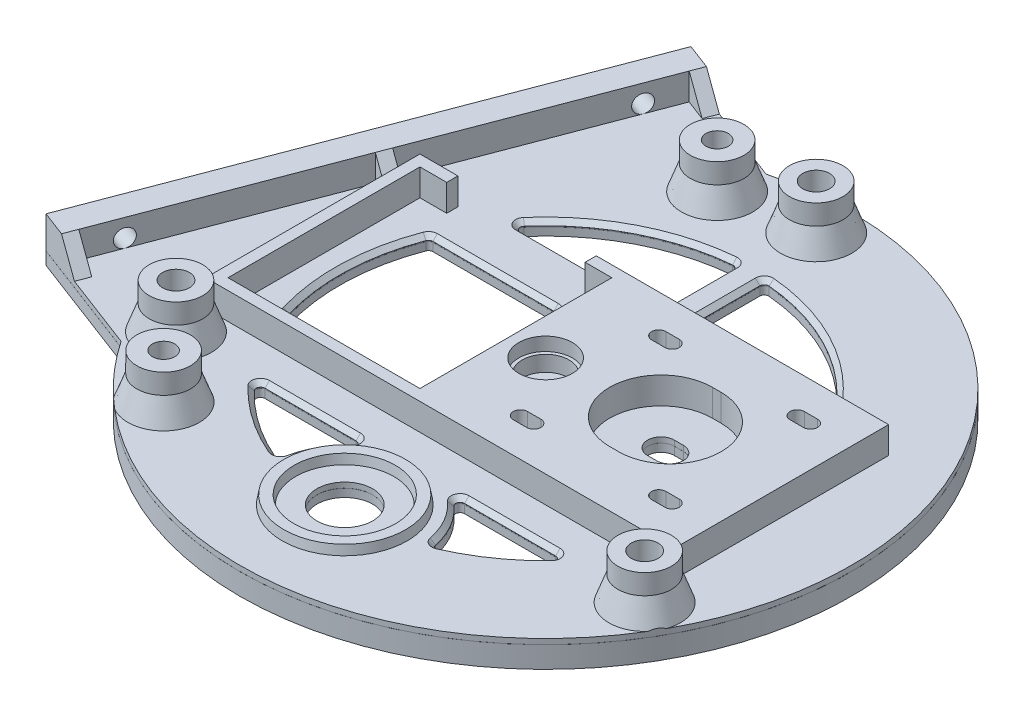
SolidWorks part; units mm, degrees
material "ABS"
ref_plane "Front Plane" through (0, 0, 0) normal (0, 0, 1) x (1, 0, 0)
ref_plane "Top Plane" through (0, 0, 0) normal (0, 1, 0) x (1, 0, 0)
ref_plane "Right Plane" through (0, 0, 0) normal (1, 0, 0) x (0, 0, -1)
sketch "Sketch1" plane through (0, 0, 0) normal (0, 0, 1) x (1, 0, 0)
  line L0 (0, 0) -> (68.5, 0)
  line L1 (68.5, 0) -> (68.5, -6)
  line L2 (68.5, -6) -> (66.5, -6)
  line L3 (66.5, -6) -> (66.5, -3)
  line L5 (53.5, -3) -> (53.5, -6)
  line L6 (53.5, -6) -> (50.5, -6)
  line L7 (50.5, -6) -> (50.5, -3)
  line L8 (50.5, -3) -> (8, -3)
  line L9 (8, -3) -> (8, -8)
  line L10 (8, -8) -> (0, -8)
  line L11 (0, -8) -> (0, 0)
  line L12 (62.3516, -3) -> (66.5, -3)
  line L13 (57.6484, -3) -> (53.5, -3)
  arc A0 (62.3516, -3) -> (57.6484, -3) centre (60, -6.6) ccw
  point P4 (67.5, -6)
  dimension "D2" = 4.3
  dimension "D1" = 60
  dimension "D3" = 6.5
  dimension "D4" = 3
  dimension "D5" = 6.5
  dimension "D6" = 3
  dimension "D7" = 2
  dimension "D8" = 50.5
  dimension "D9" = 0.6
  dimension "D10" = 8
  dimension "D11" = 8
revolve "Revolve1" add sketch "Sketch1" angle 360 about L11
sketch "Sketch2" plane through (0, 0, 0) normal (0, 1, 0) x (1, 0, 0)
  line L0 (-52.5, -30.3109) -> (0, 60.6218) construction
  line L1 (0, 60.6218) -> (52.5, -30.3109) construction
  line L2 (52.5, -30.3109) -> (-52.5, -30.3109) construction
  line L3 (0, 0) -> (0, 60.6218) construction
  line L4 (0, 0) -> (52.5, -30.3109) construction
  line L5 (0, 0) -> (-52.5, -30.3109) construction
  line L6 (0, 0) -> (0, -45) construction
  line L7 (-40.2731, -45.3109) -> (-40.2731, -30.3109) construction
  line L8 (-19.1038, 57.533) -> (-6.1134, 50.033) construction
  circle A0 centre (0, 60.6218) radius 6
  circle A1 centre (0, 60.6218) radius 3
  circle A2 centre (52.5, -30.3109) radius 6
  circle A3 centre (-52.5, -30.3109) radius 6
  circle A4 centre (-52.5, -30.3109) radius 3
  circle A5 centre (52.5, -30.3109) radius 3
  circle A6 centre (0, -45) radius 6.25 construction
  arc A7 (0, 60.6218) -> (-24.7136, -55.3555) centre (0, 0) ccw construction
  circle A8 centre (-40.2731, -45.3109) radius 6
  circle A9 centre (-19.1038, 57.533) radius 6
  circle A10 centre (-40.2731, -45.3109) radius 2.5
  circle A11 centre (-19.1038, 57.533) radius 2.5
  arc A12 (15.6635, -19.9954) -> (14.3368, 20.9671) centre (0, 0) ccw construction
  dimension "D2" = 12
  dimension "D3" = 6
  dimension "D5" = 12.5
  dimension "D6" = 12
  dimension "D8" = 5
  dimension "D9" = 25.4
  dimension "D1" = 105
  dimension "D4" = 45
  dimension "D7" = 15
extrude "Boss-Extrude1" add sketch "Sketch2" along normal blind 10
sketch "Sketch3" plane through (0, 0, 0) normal (0, 1, 0) x (1, 0, 0)
  circle A0 centre (0, -45) radius 6.25
  circle A1 centre (0, -45) radius 6.25 construction
extrude "Cut-Extrude1" cut sketch "Sketch3" against normal blind 10
sketch "Sketch12" plane through (0, 0, 0) normal (0, 1, 0) x (1, 0, 0)
  line L0 (0, 60.6218) -> (-40.2731, -45.3109) construction
  line L1 (-56.7747, -38.326) -> (-83.9292, -28.0025)
  line L2 (-83.9292, -28.0025) -> (-44.1287, 76.6871)
  line L3 (-44.1287, 76.6871) -> (-16.9742, 66.3636)
  line L4 (0, 0) -> (-64.0289, 24.3423) construction
  circle A0 centre (0, 0) radius 68.5 construction
  arc A1 (-56.7747, -38.326) -> (-16.9742, 66.3636) centre (0, 0) cw
  point P8 (-20.1366, 7.6554)
  dimension "D2" = 68.5
  dimension "D1" = 112
extrude "Boss-Extrude5" add sketch "Sketch12" against normal blind 4 contours L2 A1 L3 | L1 A1 L2 region at (-41.1369, 0, -61.2808) region at (-71.4581, 0, 18.4748)
sketch "Sketch4" plane through (0, 0, 0) normal (0, 1, 0) x (1, 0, 0)
  circle A0 centre (0, -45) radius 11
  circle A1 centre (0, -45) radius 14
  dimension "D1" = 22
  dimension "D2" = 28
extrude "Boss-Extrude2" add sketch "Sketch4" along normal blind 2 draft 10
sketch "Sketch5" plane through (0, 0, 0) normal (0, 1, 0) x (1, 0, 0)
  line L0 (51.3563, -22.5103) -> (51.3563, 25.4897)
  line L1 (51.3563, -22.5103) -> (-53.6437, -22.5103)
  line L2 (51.3563, 25.4897) -> (-53.6437, 25.4897) construction
  line L3 (-53.6437, -22.5103) -> (-53.6437, 25.4897)
  line L4 (-51.1437, 22.9897) -> (-45.1437, 22.9897)
  line L5 (-53.6437, 1.4897) -> (51.3563, 1.4897) construction
  line L6 (25.3563, 1.4897) -> (25.3563, 25.4897) construction
  line L7 (26.3563, 1.4897) -> (24.3563, 1.4897) construction
  line L8 (26.3563, -10.0103) -> (24.3563, -10.0103)
  line L9 (26.3563, 12.9897) -> (24.3563, 12.9897)
  line L10 (-45.1437, 22.9897) -> (-45.1437, 25.4897)
  line L11 (-51.1437, -20.0103) -> (-51.1437, 22.9897)
  line L12 (-51.1437, 22.9897) -> (-8.1437, 22.9897) construction
  line L13 (-8.1437, 22.9897) -> (-8.1437, -20.0103)
  line L14 (-8.1437, -20.0103) -> (-51.1437, -20.0103)
  line L15 (-45.1437, 25.4897) -> (-53.6437, 25.4897)
  line L16 (-8.1437, 22.9897) -> (-14.1437, 22.9897)
  line L17 (-14.1437, 22.9897) -> (-14.1437, 25.4897)
  line L18 (-14.1437, 25.4897) -> (51.3563, 25.4897)
  line L19 (-38.5203, 74.5549) -> (-78.3208, -30.1347)
  line L20 (-44.1287, 76.6871) -> (-16.9742, 66.3636) construction
  line L21 (-56.7747, -38.326) -> (-83.9292, -28.0025) construction
  line L22 (-78.3208, -30.1347) -> (-83.9292, -28.0025)
  line L23 (-83.9292, -28.0025) -> (-44.1287, 76.6871)
  line L24 (-83.9292, -28.0025) -> (-44.1287, 76.6871) construction
  line L25 (-44.1287, 76.6871) -> (-38.5203, 74.5549)
  arc A1 (26.3563, -10.0103) -> (26.3563, 12.9897) centre (26.3563, 1.4897) ccw
  arc A2 (24.3563, 12.9897) -> (24.3563, -10.0103) centre (24.3563, 1.4897) ccw
  arc A3 (15.6635, -19.9954) -> (14.3368, 20.9671) centre (0, 0) ccw construction
  point P10 (25.3563, 1.4897)
  point P18 (-8.1437, 1.4897)
  dimension "D3" = 23
  dimension "D1" = 48
  dimension "D2" = 105
  dimension "D4" = 2
  dimension "D5" = 26
  dimension "D6" = 2.5
  dimension "D7" = 43
  dimension "D8" = 43
  dimension "D9" = 6
  dimension "D10" = 6
  dimension "D11" = 6
extrude "Boss-Extrude3" add sketch "Sketch5" along normal blind 6
sketch "Sketch6" plane through (0, 6, 0) normal (0, 1, 0) x (1, 0, 0)
  line L0 (40.8563, -14.0103) -> (40.8563, 16.9897) construction
  line L1 (40.8563, -14.0103) -> (9.8563, -14.0103) construction
  line L2 (40.8563, 16.9897) -> (9.8563, 16.9897) construction
  line L3 (9.8563, -14.0103) -> (9.8563, 16.9897) construction
  line L4 (40.8563, -14.0103) -> (9.8563, 16.9897) construction
  line L5 (40.8563, 16.9897) -> (9.8563, -14.0103) construction
  line L6 (25.3563, 1.4897) -> (25.3563, 25.4897) construction
  line L7 (11.3563, -14.0103) -> (8.3563, -14.0103) construction
  line L8 (11.3563, -15.6103) -> (8.3563, -15.6103)
  line L9 (11.3563, -12.4103) -> (8.3563, -12.4103)
  line L10 (42.3563, -14.0103) -> (39.3563, -14.0103) construction
  line L11 (42.3563, -15.6103) -> (39.3563, -15.6103)
  line L12 (42.3563, -12.4103) -> (39.3563, -12.4103)
  line L13 (42.3563, 16.9897) -> (39.3563, 16.9897) construction
  line L14 (42.3563, 15.3897) -> (39.3563, 15.3897)
  line L15 (42.3563, 18.5897) -> (39.3563, 18.5897)
  line L16 (11.3563, 16.9897) -> (8.3563, 16.9897) construction
  line L17 (11.3563, 15.3897) -> (8.3563, 15.3897)
  line L18 (11.3563, 18.5897) -> (8.3563, 18.5897)
  arc A0 (11.3563, -15.6103) -> (11.3563, -12.4103) centre (11.3563, -14.0103) ccw
  arc A1 (8.3563, -12.4103) -> (8.3563, -15.6103) centre (8.3563, -14.0103) ccw
  arc A2 (42.3563, -15.6103) -> (42.3563, -12.4103) centre (42.3563, -14.0103) ccw
  arc A3 (39.3563, -12.4103) -> (39.3563, -15.6103) centre (39.3563, -14.0103) ccw
  arc A4 (42.3563, 15.3897) -> (42.3563, 18.5897) centre (42.3563, 16.9897) ccw
  arc A5 (39.3563, 18.5897) -> (39.3563, 15.3897) centre (39.3563, 16.9897) ccw
  arc A6 (11.3563, 15.3897) -> (11.3563, 18.5897) centre (11.3563, 16.9897) ccw
  arc A7 (8.3563, 18.5897) -> (8.3563, 15.3897) centre (8.3563, 16.9897) ccw
  point P1 (25.3563, 1.4897)
  point P2 (25.3563, 16.9897)
  point P11 (9.8563, -14.0103)
  point P21 (40.8563, -14.0103)
  point P28 (40.8563, 16.9897)
  point P35 (9.8563, 16.9897)
  dimension "D2" = 1.6
  dimension "D1" = 31
  dimension "D3" = 3
  dimension "D4" = 2
  dimension "D5" = 2
extrude "Cut-Extrude2" cut sketch "Sketch6" against normal through all
sketch "Sketch7" plane through (0, 0, 0) normal (0, 1, 0) x (1, 0, 0)
  line L0 (26.3563, 1.4897) -> (24.3563, 1.4897) construction
  line L1 (26.3563, -1.5103) -> (24.3563, -1.5103)
  line L2 (26.3563, 4.4897) -> (24.3563, 4.4897)
  arc A0 (26.3563, -1.5103) -> (26.3563, 4.4897) centre (26.3563, 1.4897) ccw
  arc A1 (24.3563, 4.4897) -> (24.3563, -1.5103) centre (24.3563, 1.4897) ccw
  point P2 (25.3563, 1.4897)
  dimension "D1" = 3
extrude "Cut-Extrude3" cut sketch "Sketch7" against normal through all
sketch "Sketch8" plane through (0, 6, 0) normal (0, 1, 0) x (1, 0, 0)
  circle A0 centre (0, 0) radius 2
  dimension "D1" = 4
extrude "Cut-Extrude4" cut sketch "Sketch8" against normal through all
chamfer "Chamfer1" distance 2 angle 45 16 edges at (37.7563, -3, 14.0103) (40.8563, -3, 12.4103) (40.8563, -3, 15.6103) (43.9563, -3, 14.0103) (37.7563, -3, -16.9897) (40.8563, -3, -18.5897) (40.8563, -3, -15.3897) (43.9563, -3, -16.9897) (6.7563, -3, -16.9897) (9.8563, -3, -18.5897) (9.8563, -3, -15.3897) (12.9563, -3, -16.9897) (6.7563, -3, 14.0103) (9.8563, -3, 12.4103) (9.8563, -3, 15.6103) (12.9563, -3, 14.0103)
sketch "Sketch9" plane through (0, 6, 0) normal (0, 1, 0) x (1, 0, 0)
  circle A0 centre (0, 0) radius 5.25
  dimension "D1" = 10.5
extrude "Cut-Extrude5" cut sketch "Sketch9" against normal blind 6.5
sketch "Sketch10" plane through (0, 6, 0) normal (0, 1, 0) x (1, 0, 0)
  circle A0 centre (0, 0) radius 6
  dimension "D1" = 12
extrude "Cut-Extrude6" cut sketch "Sketch10" against normal blind 3
sketch "Sketch11" plane through (0, 0, 0) normal (0, 1, 0) x (1, 0, 0)
  line L0 (-14.1437, -13.0103) -> (-14.1437, 15.9897)
  line L1 (-15.1437, 16.9897) -> (-42.2431, 16.9897)
  line L2 (-15.1437, -14.0103) -> (-43.2536, -14.0103)
  line L3 (-8.1437, 22.9897) -> (-8.1437, -20.0103) construction
  line L4 (-8.1437, -20.0103) -> (-51.1437, -20.0103) construction
  line L5 (-51.1437, 22.9897) -> (-8.1437, 22.9897) construction
  line L6 (-36.3293, 28.4897) -> (36.3293, 28.4897) construction
  line L7 (51.3563, 25.4897) -> (-53.6437, 25.4897) construction
  line L8 (3, 29.4897) -> (3, 44.9905)
  line L9 (-3, 29.4897) -> (-3, 44.9905)
  line L10 (-34.2126, 28.4897) -> (-4, 28.4897)
  line L11 (4, 28.4897) -> (34.2126, 28.4897)
  line L12 (52.5, -30.3109) -> (-52.5, -30.3109) construction
  line L13 (-32.5542, -30.3109) -> (-12.1463, -30.3109)
  line L14 (12.1463, -30.3109) -> (32.5542, -30.3109)
  arc A0 (-43.1783, 16.3437) -> (-44.2113, -13.2984) centre (0, 0) ccw
  arc A1 (-36.3293, 28.4897) -> (36.3293, 28.4897) centre (0, 0) cw construction
  arc A2 (-4.0886, 45.9866) -> (-34.9701, 30.1426) centre (0, 0) ccw
  arc A3 (34.9701, 30.1426) -> (4.0886, 45.9866) centre (0, 0) ccw
  arc A4 (33.2749, -32.0041) -> (18.3502, -42.3645) centre (0, 0) cw
  arc A5 (-18.3502, -42.3645) -> (-33.2749, -32.0041) centre (0, 0) cw
  arc A6 (16.9717, -41.6411) -> (11.4826, -32.0589) centre (0, -45) ccw
  arc A7 (-16.9717, -41.6411) -> (-11.4826, -32.0589) centre (0, -45) cw
  arc A8 (33.2749, -32.0041) -> (32.5542, -30.3109) centre (32.5542, -31.3109) ccw
  arc A9 (-33.2749, -32.0041) -> (-32.5542, -30.3109) centre (-32.5542, -31.3109) cw
  arc A10 (18.3502, -42.3645) -> (16.9717, -41.6411) centre (17.9527, -41.4469) cw
  arc A11 (-18.3502, -42.3645) -> (-16.9717, -41.6411) centre (-17.9527, -41.4469) ccw
  arc A12 (11.4826, -32.0589) -> (12.1463, -30.3109) centre (12.1463, -31.3109) cw
  arc A13 (-11.4826, -32.0589) -> (-12.1463, -30.3109) centre (-12.1463, -31.3109) ccw
  arc A14 (-14.1437, -13.0103) -> (-15.1437, -14.0103) centre (-15.1437, -13.0103) cw
  arc A15 (-14.1437, 15.9897) -> (-15.1437, 16.9897) centre (-15.1437, 15.9897) ccw
  arc A16 (3, 29.4897) -> (4, 28.4897) centre (4, 29.4897) ccw
  arc A17 (-3, 29.4897) -> (-4, 28.4897) centre (-4, 29.4897) cw
  arc A18 (-43.2536, -14.0103) -> (-44.2113, -13.2984) centre (-43.2536, -13.0103) cw
  arc A19 (-42.2431, 16.9897) -> (-43.1783, 16.3437) centre (-42.2431, 15.9897) ccw
  arc A20 (34.2126, 28.4897) -> (34.9701, 30.1426) centre (34.2126, 29.4897) ccw
  arc A21 (3, 44.9905) -> (4.0886, 45.9866) centre (4, 44.9905) cw
  arc A22 (-3, 44.9905) -> (-4.0886, 45.9866) centre (-4, 44.9905) ccw
  arc A23 (-34.2126, 28.4897) -> (-34.9701, 30.1426) centre (-34.2126, 29.4897) cw
  point P37 (34.8243, -30.3109)
  point P40 (-34.8243, -30.3109)
  point P47 (9.1407, -30.3109)
  point P50 (-9.1407, -30.3109)
  point P57 (3, 28.4897)
  point P60 (-3, 28.4897)
  point P70 (3, 46.0704)
  point P73 (-3, 46.0704)
  dimension "D4" = 3
  dimension "D5" = 6
  dimension "D6" = 1
  dimension "D1" = 6
  dimension "D2" = 6
  dimension "D3" = 6
extrude "Cut-Extrude7" cut sketch "Sketch11" against normal through all
sketch "Sketch13" plane through (-64.0289, 0, -24.3423) normal (-0.9347, 0, -0.3554) x (-0.3554, 0, 0.9347)
  line L0 (0, -4) -> (-56, -4) construction
  line L1 (-56, -4) -> (-56, 6) construction
  line L2 (56, -4) -> (56, 6) construction
  circle A0 centre (-45, 2) radius 2
  circle A1 centre (45, 2) radius 2
  dimension "D4" = 4
  dimension "D1" = 6
  dimension "D2" = 11
  dimension "D3" = 11
  dimension "D5" = 90
extrude "Cut-Extrude8" cut sketch "Sketch13" against normal blind 10
sketch "Sketch15" plane through (-19.9003, 0, 52.3448) normal (-0.3554, 0, 0.9347) x (0.9347, 0, 0.3554)
  line L0 (-62.5, 6) -> (-57.5, 0)
  line L1 (-39.4493, 0) -> (-62.5, 0) construction
  line L2 (-62.5, 6) -> (-62.5, 0) construction
  dimension "D1" = 5
rib "Rib1" sketch "Sketch15" sketch "Sketch15" thickness 3 extrusion direction parallel to sketch draft on no parameters "D1"=3
pattern_linear "LPattern1" count 3 spacing 54.5 along (0.3554, 0, -0.9347) of "Rib1"
chamfer "Chamfer2" distance 2 angle 70 5 edges at (-52.5, 0, 36.3109) (-19.1038, 0, -51.533) (0, 0, -54.6218) (52.5, 0, 36.3109) (-40.2731, 0, 51.3109) first distance on face at (-34.8759, 0, -13.8993)
chamfer "Chamfer3" distance 1 angle 45 32 edges at (-29.1987, 0, 14.0103) (-14.4366, 0, 13.7174) (-43.8503, 0, 13.8128) (-14.1437, 0, -1.4897) (-46.14, 0, -1.6079) (-14.4366, 0, -16.6968) (-42.8114, 0, -16.8125) (-28.6934, 0, -16.9897) (17.488, 0, 42.3324) (26.3272, 0, 37.9257) (15.0122, 0, 36.4003) (33.4743, 0, 30.9192) (11.2114, 0, 30.9559) (22.3502, 0, 30.3109) (-17.488, 0, 42.3324) (-15.0122, 0, 36.4003) (-26.3272, 0, 37.9257) (-11.2114, 0, 30.9559) (-33.4743, 0, 30.9192) (-22.3502, 0, 30.3109) (3.2929, 0, -28.7826) (19.1063, 0, -28.4897) (3, 0, -37.2401) (35.1217, 0, -29.0731) (3.3249, 0, -45.7283) (21.0749, 0, -41.0771) (-3.2929, 0, -28.7826) (-3, 0, -37.2401) (-19.1063, 0, -28.4897) (-3.3249, 0, -45.7283) (-35.1217, 0, -29.0731) (-21.0749, 0, -41.0771)
sketch "Sketch16" plane through (0, 0, 0) normal (0, 0, 1) x (1, 0, 0)
  line L1 (117.7195, -1.195) -> (-117.7195, -1.195)
  line L2 (117.7195, -1.195) -> (117.7195, -1.205)
  line L3 (117.7195, -1.205) -> (-117.7195, -1.205)
  line L4 (-117.7195, -1.195) -> (-117.7195, -1.205)
  line L5 (117.7195, -1.195) -> (-117.7195, -1.205) construction
  line L6 (117.7195, -1.205) -> (-117.7195, -1.195) construction
  point P0 (0, -1.2)
  dimension "D1" = 1.2
  dimension "D2" = 0.01
extrude "Cut-Extrude9" cut sketch "Sketch16" against normal through all both and the other way through all
